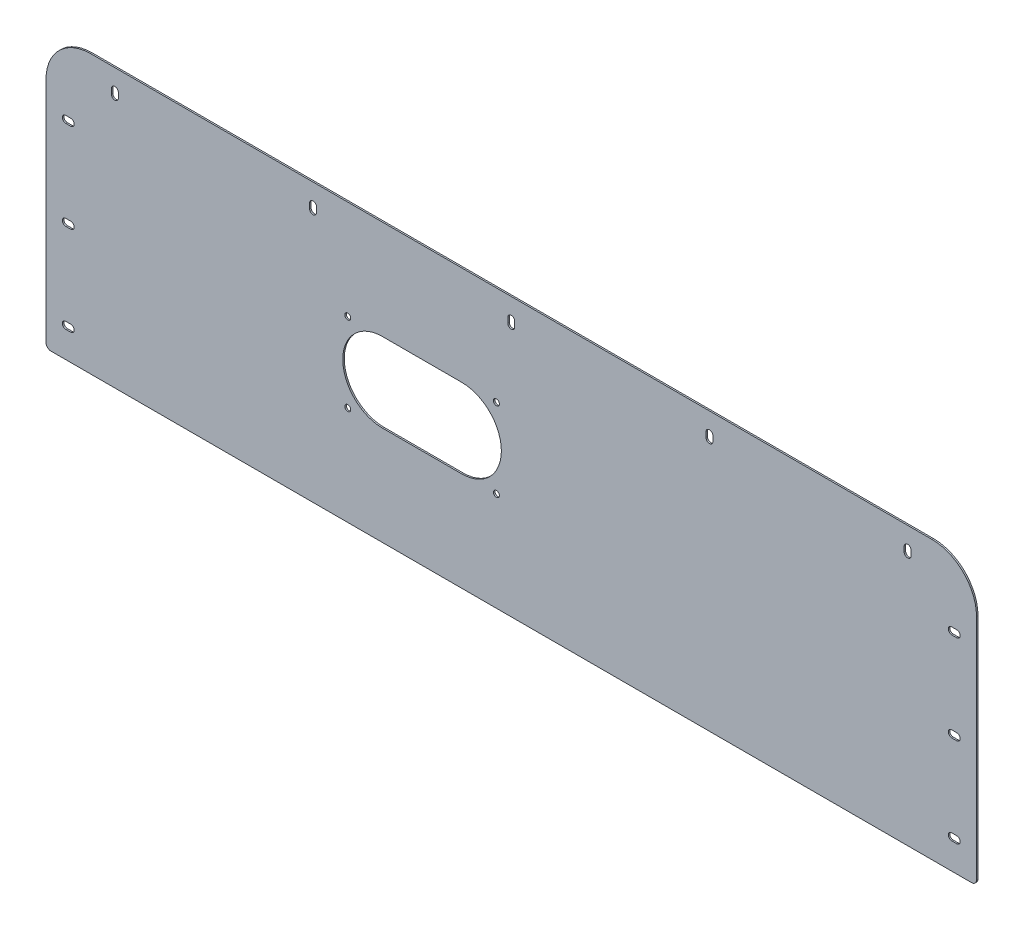
SolidWorks part; units mm, degrees
material "Q235-A"
ref_plane "前视基准面" through (0, 0, 0) normal (0, 0, 1) x (1, 0, 0)
ref_plane "上视基准面" through (0, 0, 0) normal (0, 1, 0) x (1, 0, 0)
ref_plane "右视基准面" through (0, 0, 0) normal (1, 0, 0) x (0, 0, -1)
sketch "草图1" plane through (0, 0, 0) normal (0, 0, 1) x (1, 0, 0)
  line L1 (469.5, -140) -> (-469.5, -140)
  line L2 (469.5, -140) -> (469.5, 140)
  line L3 (469.5, 140) -> (-469.5, 140)
  line L4 (-469.5, -140) -> (-469.5, 140)
  line L5 (469.5, -140) -> (-469.5, 140) construction
  line L6 (469.5, 140) -> (-469.5, -140) construction
  point P0 (0, 0)
  dimension "D1" = 939
  dimension "D2" = 280
base flange "基体-法兰1" sketch "草图1" thickness 1.5 reverse thickness direction no parameters "D1"=0.7366
sketch "草图33" plane through (0, 0, -1.5) normal (0, 0, -1) x (-1, 0, 0)
  line L0 (0, 0) -> (-544.0361, 0) construction
  line L5 (50, 0) -> (130, 0) construction
  line L10 (50, 40) -> (130, 40)
  line L11 (50, -40) -> (130, -40)
  line L12 (0, 0) -> (484.2374, 0) construction
  arc A0 (50, 40) -> (50, -40) centre (50, 0) ccw
  arc A1 (130, -40) -> (130, 40) centre (130, 0) ccw
  point P1 (90, 0)
  dimension "D3" = 50
  dimension "D1" = 80
  dimension "D2" = 80
extrude "切除-拉伸1" cut sketch "草图33" against normal blind 10 normal cut yes
fillet "圆角1" radius 45 2 edges at (469.5, 140, -0.75) (-469.5, 140, -0.75)
fillet "圆角2" radius 5 2 edges at (469.5, -140, -0.75) (-469.5, -140, -0.75)
sketch "草图34" plane through (0, 0, -1.5) normal (0, 0, -1) x (-1, 0, 0)
  line L0 (-400, 120) -> (-400, 115) construction
  line L1 (-396.5, 120) -> (-396.5, 115)
  line L2 (-403.5, 120) -> (-403.5, 115)
  line L3 (-424.5, 140) -> (424.5, 140) construction
  line L4 (-469.5, -135) -> (-469.5, 95) construction
  arc A0 (-396.5, 120) -> (-403.5, 120) centre (-400, 120) ccw
  arc A1 (-403.5, 115) -> (-396.5, 115) centre (-400, 115) ccw
  point P2 (-400, 117.5)
  dimension "D1" = 7
  dimension "D2" = 5
  dimension "D3" = 22.5
  dimension "D4" = 69.5
extrude "切除-拉伸2" cut sketch "草图34" against normal blind 10 normal cut yes
pattern_linear "阵列(线性)1" count 5 spacing 200 along (-1, 0, 0) of "切除-拉伸2"
sketch "草图35" plane through (0, 0, -1.5) normal (0, 0, -1) x (-1, 0, 0)
  line L0 (-449.5, -110) -> (-444.5, -110) construction
  line L1 (-449.5, -106.5) -> (-444.5, -106.5)
  line L2 (-449.5, -113.5) -> (-444.5, -113.5)
  line L3 (-469.5, -135) -> (-469.5, 95) construction
  line L4 (464.5, -140) -> (-464.5, -140) construction
  line L5 (444.5, -110) -> (449.5, -110) construction
  line L6 (444.5, -106.5) -> (449.5, -106.5)
  line L7 (444.5, -113.5) -> (449.5, -113.5)
  line L8 (469.5, 95) -> (469.5, -135) construction
  arc A0 (-449.5, -106.5) -> (-449.5, -113.5) centre (-449.5, -110) ccw
  arc A1 (-444.5, -113.5) -> (-444.5, -106.5) centre (-444.5, -110) ccw
  arc A2 (444.5, -106.5) -> (444.5, -113.5) centre (444.5, -110) ccw
  arc A3 (449.5, -113.5) -> (449.5, -106.5) centre (449.5, -110) ccw
  point P2 (-447, -110)
  point P13 (447, -110)
  dimension "D1" = 7
  dimension "D2" = 5
  dimension "D3" = 22.5
  dimension "D4" = 30
  dimension "D5" = 7
  dimension "D6" = 5
  dimension "D7" = 22.5
extrude "切除-拉伸3" cut sketch "草图35" against normal blind 10 normal cut yes
pattern_linear "阵列(线性)2" count 3 spacing 90 along (0, 1, 0) of "切除-拉伸3"
sketch "草图36" plane through (0, 0, -1.5) normal (0, 0, -1) x (-1, 0, 0)
  line L0 (130, 40) -> (50, 40) construction
  circle A0 centre (15, 40) radius 3
  circle A1 centre (165, 40) radius 3
  circle A2 centre (165, -40) radius 3
  circle A3 centre (15, -40) radius 3
  point P11 (90, 40)
  dimension "D5" = 6
  dimension "D1" = 150
  dimension "D2" = 80
  dimension "D3" = 40
  dimension "D4" = 75
extrude "切除-拉伸4" cut sketch "草图36" against normal blind 10 normal cut yes
sketch "折弯-线1" [suppressed] plane through (0, 0, 0) normal (0, 1, 0) x (1, 0, 0)
sketch "边界框1" [suppressed] plane through (0, 0, 0) normal (0, 1, 0) x (1, 0, 0)
sheet metal parameters "钣金1" thickness 1.5 parameters "D1"=0.7366
flat pattern "平板型式1" [suppressed]
sketch "折弯-线2" plane through (0, 0, 0) normal (0, 1, 0) x (1, 0, 0)
sketch3d "边界框2" [suppressed]
  line L0 (100, -90, 0) -> (-100, -90, 0) construction
  line L1 (100, 90, 0) -> (-100, 90, 0) construction
  line L2 (100, -90, 0) -> (100, 90, 0) construction
  line L3 (-100, -90, 0) -> (-100, 90, 0) construction
sheet metal parameters "钣金4" thickness 1.5 parameters "D1"=0.7366
flat pattern "平板型式1"
sketch "折弯-线2" plane through (0, 0, 0) normal (0, 0, 1) x (1, 0, 0)
sketch3d "边界框2" [suppressed]
  line L0 (-469.5, 140, 0) -> (469.5, 140, 0) construction
  line L1 (-469.5, -140, 0) -> (469.5, -140, 0) construction
  line L2 (-469.5, 140, 0) -> (-469.5, -140, 0) construction
  line L3 (469.5, 140, 0) -> (469.5, -140, 0) construction
sheet metal parameters "钣金5" thickness 1.5 parameters "D1"=0.7366
flat pattern "平板型式1"
sketch "折弯-线2" plane through (0, 0, 0) normal (0, 0, 1) x (1, 0, 0)
sketch3d "边界框2" [suppressed]
  line L0 (-469.5, 140, 0) -> (469.5, 140, 0) construction
  line L1 (-469.5, -140, 0) -> (469.5, -140, 0) construction
  line L2 (-469.5, 140, 0) -> (-469.5, -140, 0) construction
  line L3 (469.5, 140, 0) -> (469.5, -140, 0) construction
sheet metal parameters "钣金6" thickness 1.5 parameters "D1"=0.7366
flat pattern "平板型式1"
sketch "折弯-线2" plane through (0, 0, 0) normal (0, 0, 1) x (1, 0, 0)
sketch3d "边界框2" [suppressed]
  line L0 (-469.5, 140, 0) -> (469.5, 140, 0) construction
  line L1 (-469.5, -140, 0) -> (469.5, -140, 0) construction
  line L2 (-469.5, 140, 0) -> (-469.5, -140, 0) construction
  line L3 (469.5, 140, 0) -> (469.5, -140, 0) construction
sheet metal parameters "钣金7" thickness 1.5 parameters "D1"=0.7366
flat pattern "平板型式1"
sketch "折弯-线2" plane through (0, 0, 0) normal (0, 0, 1) x (1, 0, 0)
sketch3d "边界框2" [suppressed]
  line L0 (-469.5, 140, 0) -> (469.5, 140, 0) construction
  line L1 (-469.5, -140, 0) -> (469.5, -140, 0) construction
  line L2 (-469.5, 140, 0) -> (-469.5, -140, 0) construction
  line L3 (469.5, 140, 0) -> (469.5, -140, 0) construction
sheet metal parameters "钣金8" thickness 1.5 parameters "D1"=0.7366
flat pattern "平板型式1"
sketch "折弯-线2" plane through (0, 0, 0) normal (0, 0, 1) x (1, 0, 0)
sketch3d "边界框2" [suppressed]
  line L0 (-469.5, 140, 0) -> (469.5, 140, 0) construction
  line L1 (-469.5, -140, 0) -> (469.5, -140, 0) construction
  line L2 (-469.5, 140, 0) -> (-469.5, -140, 0) construction
  line L3 (469.5, 140, 0) -> (469.5, -140, 0) construction
sheet metal parameters "钣金9" thickness 1.5 parameters "D1"=0.7366
flat pattern "平板型式1"
sketch "折弯-线2" plane through (0, 0, 0) normal (0, 0, 1) x (1, 0, 0)
sketch3d "边界框2" [suppressed]
  line L0 (-469.5, 140, 0) -> (469.5, 140, 0) construction
  line L1 (-469.5, -140, 0) -> (469.5, -140, 0) construction
  line L2 (-469.5, 140, 0) -> (-469.5, -140, 0) construction
  line L3 (469.5, 140, 0) -> (469.5, -140, 0) construction
